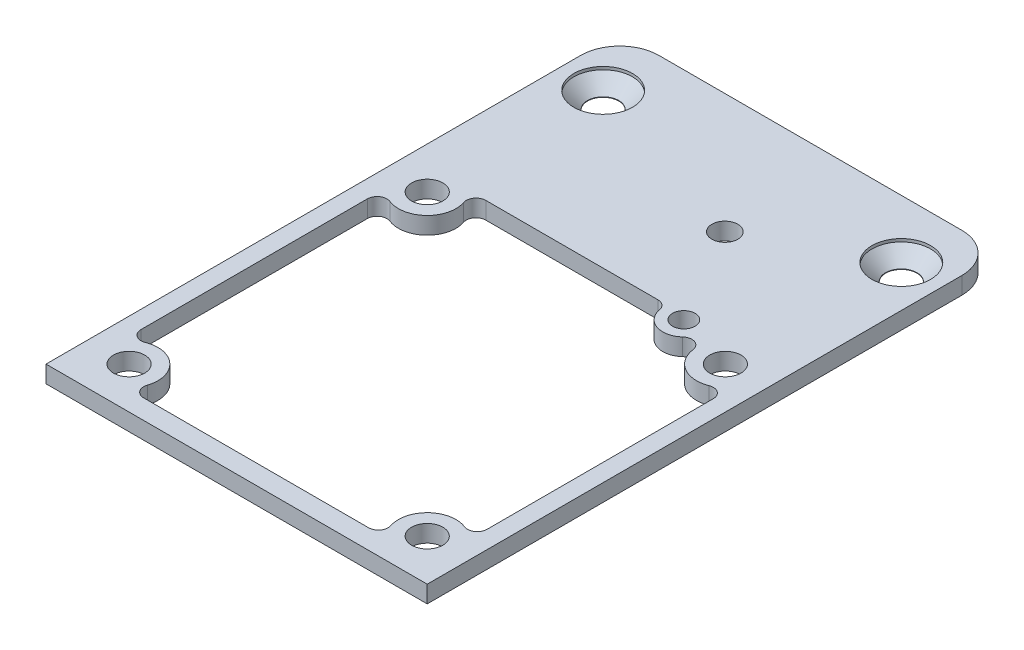
SolidWorks part; units mm, degrees
ref_plane "Front Plane" through (0, 0, 0) normal (0, 0, 1) x (1, 0, 0)
ref_plane "Top Plane" through (0, 0, 0) normal (0, 1, 0) x (1, 0, 0)
ref_plane "Right Plane" through (0, 0, 0) normal (1, 0, 0) x (0, 0, -1)
sketch "Sketch1" plane through (0, 0, 0) normal (0, 1, 0) x (1, 0, 0)
  line L0 (-15.5, 39.2) -> (15.5, 39.2)
  line L1 (-18.2, 15) -> (-18.2, -15) construction
  line L2 (17.7, -17.4996) -> (-17.7, -17.4996)
  line L3 (17.7, -17.4996) -> (17.7, 17.4996)
  line L4 (17.7, 17.4996) -> (-17.7, 17.4996)
  line L5 (-17.7, -17.4996) -> (-17.7, 17.4996)
  line L6 (17.7, -17.4996) -> (-17.7, 17.4996) construction
  line L7 (-19.5, 35.2) -> (-19.5, -19.5)
  line L8 (-19.5, -19.5) -> (19.5, -19.5)
  line L9 (19.5, -19.5) -> (19.5, 35.2)
  line L10 (17.7, 17.4996) -> (-17.7, -17.4996) construction
  line L11 (-15.25, 15.25) -> (-15.25, 17.9996) construction
  line L12 (11.35, 17.05) -> (11.35, 17.4996)
  line L13 (7.05, 17.05) -> (7.05, 17.4996)
  arc A0 (19.5, 35.2) -> (15.5, 39.2) centre (15.5, 35.2) ccw construction
  arc A1 (-15.5, 39.2) -> (-19.5, 35.2) centre (-15.5, 35.2) ccw construction
  arc A2 (19.5, 35.2) -> (15.5, 39.2) centre (15.5, 35.2) ccw
  arc A3 (-15.5, 39.2) -> (-19.5, 35.2) centre (-15.5, 35.2) ccw
  circle A4 centre (-15.25, -15.25) radius 1.6 construction
  circle A5 centre (15.25, -15.25) radius 1.6 construction
  circle A6 centre (-15.25, 15.25) radius 1.6 construction
  circle A7 centre (15.25, 15.25) radius 1.6 construction
  circle A8 centre (-15.25, 33.25) radius 1.6 construction
  circle A9 centre (15.25, 33.25) radius 1.6 construction
  circle A10 centre (-15.25, -15.25) radius 1.6
  circle A11 centre (15.25, -15.25) radius 1.6
  circle A12 centre (-15.25, 15.25) radius 1.6
  circle A13 centre (15.25, 15.25) radius 1.6
  circle A14 centre (-15.25, 33.25) radius 1.6
  circle A15 centre (15.25, 33.25) radius 1.6
  arc A16 (-15.2, 18) -> (-18.2, 15) centre (-15.2, 15) ccw construction
  circle A17 centre (-15.25, 15.25) radius 2.95
  circle A18 centre (15.25, 15.25) radius 2.95
  circle A19 centre (-15.25, -15.25) radius 2.95
  circle A20 centre (15.25, -15.25) radius 2.95
  circle A21 centre (3.5, 26.95) radius 1.33 construction
  circle A22 centre (9.2, 17.05) radius 2.15
  circle A23 centre (9.2, 17.05) radius 1.15
  circle A24 centre (9.2, 17.05) radius 0.9 construction
  circle A25 centre (3.5, 26.95) radius 1.33
  circle A26 centre (11.334, 14.733) radius 1
  point P29 (0, 0)
  point P59 (11.5364, 15.4967)
  point P60 (11.1711, 14.3138)
  dimension "D3" = 2.3
  dimension "D4" = 1
  dimension "D5" = 2
  dimension "D1" = 0.5
  dimension "D2" = 0.5
extrude "Base shape" add sketch "Sketch1" along normal blind 1.75 contours L0 A3 L7 L8 L9 A2 A20 L3 L2 A19 L5 A17 L4 A18 A15 A14 | A17 L4 L5 | L4 A17 L5 A12 | L5 A17 | L4 A17 | L3 A18 L4 A13 | L3 A18 | L4 A18 | L2 A19 L5 A10 | L2 A19 | L5 A19 | A19 L5 L2 | L2 A20 L3 A11 | L3 A20 | L2 A20 | A20 L2 L3 | A18 L3 L4 | A23 L4 A22 | A23 L4 A22 | A22 L4 L13 | A22 L12 L4 | A26 A18 L4 L12 A22 region at (-0.0683, 0, -21.4041) region at (17.5279, 0, 17.307) region at (15.25, 0, 17.7828) region at (15.25, 0, 17.4246) region at (17.9015, 0, 15.25) region at (-15.25, 0, 17.7828) region at (-15.25, 0, 17.4246) region at (14.5952, 0, -12.4505) region at (17.9015, 0, -15.25) region at (-17.5279, 0, 17.307) region at (17.5279, 0, -17.307) region at (11.9929, 0, -16.5859) region at (-17.9015, 0, 15.25) region at (15.25, 0, -17.7828) region at (8.3568, 0, -15.127) region at (-17.9015, 0, -15.25) region at (-17.625, 0, -15.25) region at (11.3358, 0, -17.3874) region at (7.0642, 0, -17.3874) region at (-17.5279, 0, -17.307) region at (9.2, 0, -18.3154) region at (-15.25, 0, -17.7828)
fillet "Milling fillets" radius 1 8 edges at (-17.7, 0.875, 13.6068) (-13.3416, 0.875, 17.4996) (13.3416, 0.875, 17.4996) (17.7, 0.875, 13.6068) (17.7, 0.875, -13.6068) (-13.3416, 0.875, -17.4996) (-17.7, 0.875, -13.6068) (7.05, 0.875, -17.4996)
sketch "Sketch3" plane through (0, 1.75, 0) normal (0, 1, 0) x (1, 0, 0)
  circle A0 centre (-15.25, 33.25) radius 3
  circle A1 centre (15.25, 33.25) radius 3
  dimension "D1" = 6
extrude "Screw head cut" cut sketch "Sketch3" against normal blind 0.3
chamfer "Screw head chamfer" distance 1.4 angle 45 2 edges at (15.25, 1.45, -31.65) (-15.25, 1.45, -31.65)
